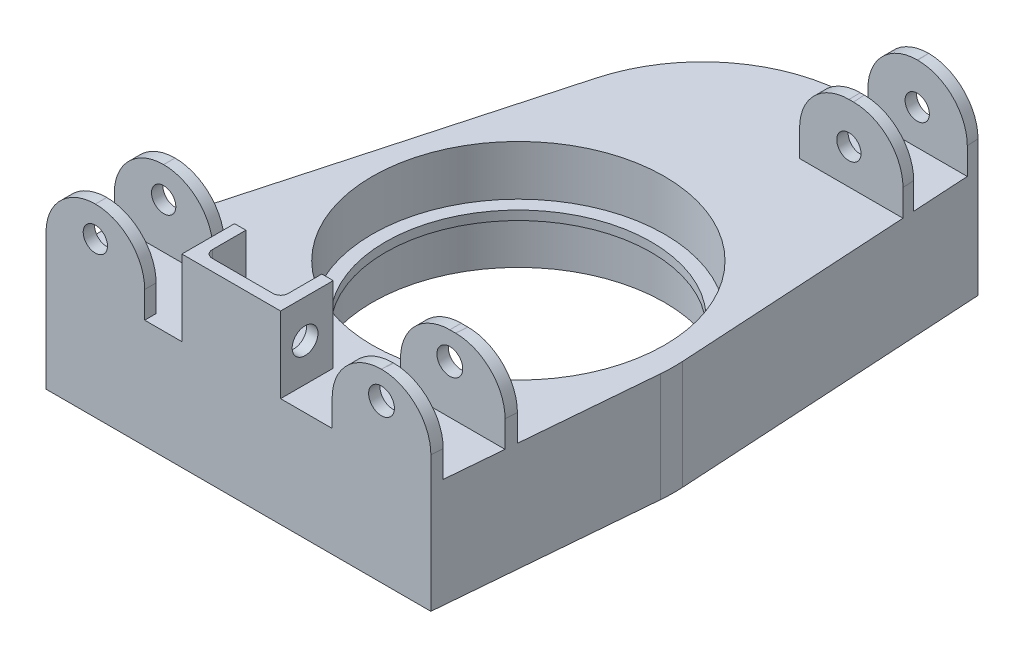
SolidWorks part; units mm, degrees
ref_plane "Front Plane" through (0, 0, 0) normal (0, 0, 1) x (1, 0, 0)
ref_plane "Top Plane" through (0, 0, 0) normal (0, 1, 0) x (1, 0, 0)
ref_plane "Right Plane" through (0, 0, 0) normal (1, 0, 0) x (0, 0, -1)
sketch "Sketch1" plane through (0, 0, 0) normal (0, 1, 0) x (1, 0, 0)
  line L0 (-78.3166, -79.7284) -> (50.4493, -79.7284)
  line L1 (56.8393, -5.2886) -> (50.4493, 103.3395)
  line L2 (50.4493, 103.3395) -> (9.0638, 103.3395)
  line L3 (-39.909, 66.0414) -> (-72.7449, -53.0584)
  line L4 (50.4493, 103.3395) -> (50.4493, -79.7284) construction
  line L5 (50.4493, -79.7284) -> (56.8393, -5.2886)
  line L6 (-78.3166, -79.7284) -> (-78.3166, -53.0584)
  line L7 (-78.3166, -53.0584) -> (-72.7449, -53.0584)
  circle A0 centre (0, 0) radius 48.895
  circle A2 centre (0, 0) radius 120.65
  arc A3 (9.0638, 103.3395) -> (-39.909, 66.0414) centre (9.0638, 52.5395) ccw
  point P10 (0, -48.895)
  point P11 (48.895, 0)
  point P15 (0, 0)
  point P16 (-48.895, 0)
  dimension "D2" = 97.79
  dimension "D3" = 7.62
  dimension "D4" = 8.89
  dimension "D5" = 26.67
  dimension "D1" = 241.3
  dimension "D6" = 50.8
extrude "Base" add sketch "Sketch1" along normal blind 36.5 contours L2 L3 L0 L1 A0 | L1 L4 A0 L5 region at (-76.0411, 0, 66.3934)
sketch "Sketch2" plane through (0, 36.5, 0) normal (0, 1, 0) x (1, 0, 0)
  line L0 (50.4493, 103.3395) -> (50.6734, 99.5295)
  line L1 (56.8393, -5.2886) -> (50.4493, 103.3395) construction
  line L2 (50.6734, 99.5295) -> (17.4293, 99.5295)
  line L3 (17.4293, 99.5295) -> (17.4293, 103.3395)
  line L4 (50.4493, 103.3395) -> (9.0638, 103.3395) construction
  line L5 (17.4293, 103.3395) -> (50.4493, 103.3395)
  line L6 (17.4293, -75.9184) -> (50.7764, -75.9184)
  line L7 (50.7764, -75.9184) -> (50.4493, -79.7284)
  line L8 (-78.3166, -79.7284) -> (50.4493, -79.7284) construction
  line L9 (50.4493, -79.7284) -> (17.4293, -79.7284)
  line L10 (17.4293, -79.7284) -> (17.4293, -75.9184)
  line L11 (17.4293, 103.3395) -> (17.4293, -79.7284) construction
  line L12 (50.4493, -79.7284) -> (56.8393, -5.2886) construction
  line L13 (17.4293, 80.4795) -> (17.4293, 76.6695)
  line L14 (17.4293, 76.6695) -> (52.0182, 76.6695)
  line L15 (52.0182, 76.6695) -> (51.794, 80.4795)
  line L16 (51.794, 80.4795) -> (17.4293, 80.4795)
  line L17 (-78.3166, -79.7284) -> (-78.3166, -53.0584) construction
  line L18 (17.4293, -53.0584) -> (52.7387, -53.0584)
  line L19 (17.4293, -53.0584) -> (17.4293, -56.8684)
  line L20 (17.4293, -56.8684) -> (52.4116, -56.8684)
  line L21 (52.7387, -53.0584) -> (52.4116, -56.8684)
  line L22 (-45.2966, -53.0584) -> (-78.3166, -53.0584)
  line L23 (-45.2966, -53.0584) -> (-45.2966, -56.8684)
  line L24 (-45.2966, -56.8684) -> (-78.3166, -56.8684)
  line L25 (-78.3166, -53.0584) -> (-78.3166, -56.8684)
  line L26 (-45.2966, -79.7284) -> (-45.2966, -60.0458) construction
  line L27 (-78.3166, -75.9184) -> (-45.2966, -75.9184)
  line L28 (-78.3166, -75.9184) -> (-78.3166, -79.7284)
  line L29 (-78.3166, -79.7284) -> (-45.2966, -79.7284)
  line L30 (-45.2966, -75.9184) -> (-45.2966, -79.7284)
  line L31 (-78.3166, -79.7284) -> (50.4493, -79.7284) construction
  dimension "D1" = 33.02
  dimension "D2" = 3.81
  dimension "D3" = 3.81
  dimension "D4" = 19.05
  dimension "D5" = 3.81
  dimension "D6" = 3.81
  dimension "D7" = 19.05
  dimension "D8" = 33.02
  dimension "D9" = 3.81
  dimension "D10" = 3.81
extrude "A-Arms" add sketch "Sketch2" along normal blind 25.4
fillet "Fillet a-arm tab f" radius 16.51 12 edges at (50.6128, 61.9, 77.8234) (52.5752, 61.9, 54.9634) (17.4293, 61.9, 77.8234) (17.4293, 61.9, 54.9634) (51.9061, 61.9, -78.5745) (50.5614, 61.9, -101.4345) (17.4293, 61.9, -78.5745) (17.4293, 61.9, -101.4345) (-78.3166, 61.9, 77.8234) (-45.2966, 61.9, 77.8234) (-45.2966, 61.9, 54.9634) (-78.3166, 61.9, 54.9634)
fillet "Fillet2" radius 50.8 1 edges at (56.8393, 18.25, 5.2886)
ref_plane "Plane1" through (0, 1, 0) normal (0, -1, 0) x (-1, 0, 0)
sketch "Sketch3" plane through (0, 1, 0) normal (0, -1, 0) x (-1, 0, 0)
  line L0 (43.8545, 51.7309) -> (51.7371, 53.9041)
  line L1 (39.909, 66.0414) -> (72.7449, -53.0584) construction
  line L2 (63.9719, -21.2377) -> (72.1885, -18.9724)
  line L3 (54.0145, 33.5988) -> (63.3923, -0.4157)
  line L4 (43.8545, 51.7309) -> (63.9719, -21.2377)
  circle A0 centre (0, 0) radius 71.12
  circle A1 centre (53.7624, 46.5582) radius 4.191
  circle A2 centre (70.1632, -11.6265) radius 4.191
  arc A3 (56.852, 39.5926) -> (51.7371, 53.9041) centre (53.7624, 46.5582) ccw
  arc A4 (72.1885, -18.9724) -> (69.039, -4.0899) centre (70.1632, -11.6265) ccw
  arc A5 (63.3923, -0.4157) -> (69.039, -4.0899) centre (68.2896, 0.9345) ccw
  arc A6 (54.0145, 33.5988) -> (56.852, 39.5926) centre (58.9118, 34.949) cw
  dimension "D1" = 60.452
  dimension "D2" = 142.24
  dimension "D3" = 8.382
  dimension "D4" = 8.382
  dimension "D5" = 15.24
  dimension "D6" = 15.24
  dimension "D7" = 5.08
extrude "Boss-Extrude3" add sketch "Sketch3" against normal blind 10 contours L3 A6 A3 A0 A1 L0 L4 L2 A2 A4 A5 | A0 A3 L0 A1 | L2 A4 A0 A2 region at (-57.0001, 1, -15.6865) region at (-49.7533, 1, -53.1565) region at (-69.0083, 1, 17.9571)
fillet "Fillet3" radius 12.7 2 edges at (-43.8545, 6, -51.7309) (-63.9719, 6, 21.2377)
sketch "Sketch6" plane through (0, 0, -103.3395) normal (0, 0, -1) x (-1, 0, 0)
  line L0 (-33.9251, 61.9) -> (-33.9251, 40.2979) construction
  circle A1 centre (-33.9251, 48.2) radius 4.064
  dimension "D1" = 13.7
  dimension "D2" = 8.128
extrude "Tab Holes 1" cut sketch "Sketch6" against normal blind 38.1
sketch "Sketch7" plane through (0, 0, 53.0584) normal (0, 0, -1) x (-1, 0, 0)
  line L0 (61.8066, 61.9) -> (61.8066, 41.58) construction
  circle A0 centre (61.8066, 51.74) radius 4.064
  dimension "D1" = 10.16
  dimension "D2" = 8.128
extrude "Tab Holes 2" cut sketch "Sketch7" against normal through all
ref_plane "midplane" through (0, 18.25, 0) normal (0, 1, 0) x (1, 0, 0)
sketch "Sketch8" plane through (0, 18.25, 0) normal (0, 1, 0) x (1, 0, 0)
  circle A0 centre (0, 0) radius 48.895
  circle A1 centre (0, 0) radius 44.45
extrude "mid-feature bearing" add sketch "Sketch8" along normal blind 1.524 and the other way blind 1.524
sketch "Sketch9" plane through (0, 36.5, 0) normal (0, 1, 0) x (1, 0, 0)
  line L0 (-45.2966, -79.7284) -> (17.4293, -79.7284) construction
  line L1 (-32.844, -79.7284) -> (0.176, -79.7284)
  line L2 (-32.844, -79.7284) -> (-32.844, -75.9184)
  line L3 (-32.844, -75.9184) -> (0.176, -75.9184)
  line L4 (0.176, -79.7284) -> (0.176, -75.9184)
  line L6 (0.176, -75.9184) -> (-3.634, -75.9184)
  line L7 (0.176, -75.9184) -> (0.176, -62.1226)
  line L8 (0.176, -62.1226) -> (-3.634, -62.1226)
  line L9 (-3.634, -75.9184) -> (-3.634, -62.1226)
  line L10 (-32.844, -75.9184) -> (-29.034, -75.9184)
  line L11 (-32.844, -75.9184) -> (-32.844, -62.1226)
  line L12 (-32.844, -62.1226) -> (-29.034, -62.1226)
  line L13 (-29.034, -75.9184) -> (-29.034, -62.1226)
  line M30 (-45.2966, -79.7284) -> (17.4293, -79.7284)
  dimension "D1" = 3.81
  dimension "D2" = 3.81
  dimension "D3" = 3.81
  dimension "D4" = 25.4
extrude "Boss-Extrude5" add sketch "Sketch9" along normal blind 25.4 contours L3 L13 L12 L11 | L4 L3 L2 M30 | L9 L3 L7 L8 region at (-16.334, 36.5, 77.8234) region at (-30.939, 36.5, 69.0205) region at (-1.729, 36.5, 69.0205)
fillet "Pushrod Str" radius 2.54 2 edges at (-3.634, 49.2, 75.9184) (-29.034, 49.2, 75.9184)
sketch "Sketch10" plane through (-32.844, 0, 0) normal (-1, 0, 0) x (0, 0, 1)
  line L0 (62.1226, 49.2) -> (80.5175, 49.2) construction
  line L1 (62.1226, 61.9) -> (62.1226, 36.5) construction
  circle A0 centre (71.5365, 49.2) radius 4.318
extrude "Pushrod Holes" cut sketch "Sketch10" against normal through all
mirror "Mirror2" [suppressed] of bodies 108
delete or keep bodies "Body-Delete/Keep 1" [suppressed] type delete bodies bodies 108
sketch "Sketch11" plane through (0, 0, 79.7284) normal (0, 0, -1) x (-1, 0, 0)
  line L0 (-33.9393, 61.9) -> (-33.9393, 36.5) construction
  line L2 (-17.4293, 36.5) -> (-50.4493, 36.5) construction
  line L3 (-50.4493, 45.39) -> (-50.4493, 0) construction
  circle A0 centre (-33.9393, 52.74) radius 4.318
  arc A1 (-17.4293, 45.39) -> (-33.909, 61.9) centre (-33.9393, 45.39) ccw construction
  dimension "D1" = 9.16
extrude "Tab Holes 3" cut sketch "Sketch11" along normal blind 50.8
ref_plane "Plane2" through (0, 0, -90.0045) normal (0, 0, -1) x (-1, 0, 0)
ref_axis "Axis1" through (33.9251, 48.2, -76.6695) along (0, 0, -1)
ref_point "top wishbont att pt"
